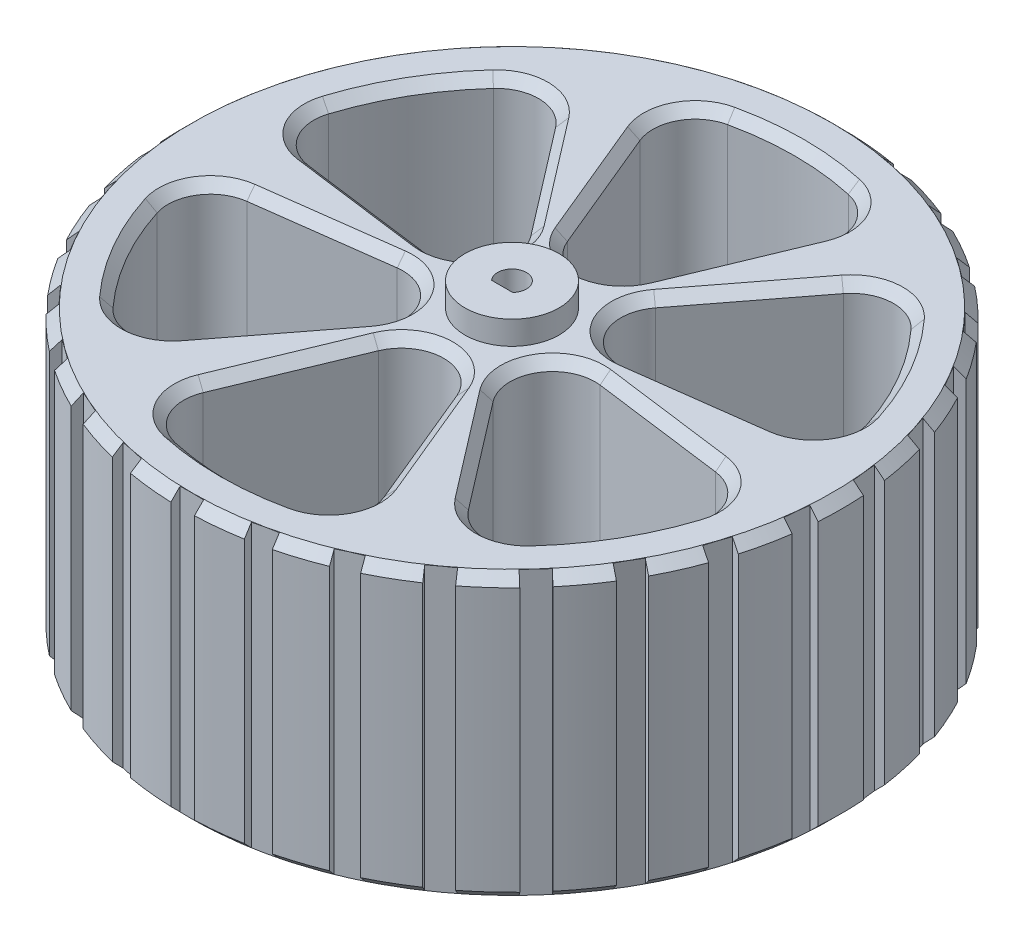
SolidWorks part; units mm, degrees
ref_plane "Front Plane" through (0, 0, 0) normal (0, 0, 1) x (1, 0, 0)
ref_plane "Top Plane" through (0, 0, 0) normal (0, 1, 0) x (1, 0, 0)
ref_plane "Right Plane" through (0, 0, 0) normal (1, 0, 0) x (0, 0, -1)
sketch "Sketch1" plane through (0, 0, 0) normal (0, 1, 0) x (1, 0, 0)
  line L0 (0, 0) -> (0, 30) construction
  line L1 (-4.1575, 10.037) -> (-9.6053, 23.1892)
  line L2 (4.1575, 10.037) -> (9.6053, 23.1892)
  line L3 (6.6136, 8.619) -> (15.2798, 19.913)
  line L4 (10.771, 1.418) -> (24.8851, 3.2762)
  line L5 (10.771, -1.418) -> (24.8851, -3.2762)
  line L6 (6.6136, -8.619) -> (15.2798, -19.913)
  line L7 (4.1575, -10.037) -> (9.6053, -23.1892)
  line L8 (-4.1575, -10.037) -> (-9.6053, -23.1892)
  line L9 (-6.6136, -8.619) -> (-15.2798, -19.913)
  line L10 (-10.771, -1.418) -> (-24.8851, -3.2762)
  line L11 (-10.771, 1.418) -> (-24.8851, 3.2762)
  line L12 (-6.6136, 8.619) -> (-15.2798, 19.913)
  arc A0 (6.4092, 29.3074) -> (-6.4092, 29.3074) centre (0, 0) ccw
  circle A1 centre (0, 0) radius 35
  arc A2 (-4.1575, 10.037) -> (4.1575, 10.037) centre (0, 11.7591) ccw
  arc A3 (9.6053, 23.1892) -> (6.4092, 29.3074) centre (5.4478, 24.9113) ccw
  arc A4 (-9.6053, 23.1892) -> (-6.4092, 29.3074) centre (-5.4478, 24.9113) cw
  arc A5 (28.5855, 9.1032) -> (22.1763, 20.2042) centre (0, 0) ccw
  arc A6 (15.2798, 19.913) -> (22.1763, 20.2042) centre (18.8499, 17.1736) cw
  arc A7 (24.8851, 3.2762) -> (28.5855, 9.1032) centre (24.2977, 7.7377) ccw
  arc A8 (6.6136, 8.619) -> (10.771, 1.418) centre (10.1837, 5.8795) ccw
  arc A9 (22.1763, -20.2042) -> (28.5855, -9.1032) centre (0, 0) ccw
  arc A10 (24.8851, -3.2762) -> (28.5855, -9.1032) centre (24.2977, -7.7377) cw
  arc A11 (15.2798, -19.913) -> (22.1763, -20.2042) centre (18.8499, -17.1736) ccw
  arc A12 (10.771, -1.418) -> (6.6136, -8.619) centre (10.1837, -5.8795) ccw
  arc A13 (-6.4092, -29.3074) -> (6.4092, -29.3074) centre (0, 0) ccw
  arc A14 (9.6053, -23.1892) -> (6.4092, -29.3074) centre (5.4478, -24.9113) cw
  arc A15 (-9.6053, -23.1892) -> (-6.4092, -29.3074) centre (-5.4478, -24.9113) ccw
  arc A16 (4.1575, -10.037) -> (-4.1575, -10.037) centre (0, -11.7591) ccw
  arc A17 (-28.5855, -9.1032) -> (-22.1763, -20.2042) centre (0, 0) ccw
  arc A18 (-15.2798, -19.913) -> (-22.1763, -20.2042) centre (-18.8499, -17.1736) cw
  arc A19 (-24.8851, -3.2762) -> (-28.5855, -9.1032) centre (-24.2977, -7.7377) ccw
  arc A20 (-6.6136, -8.619) -> (-10.771, -1.418) centre (-10.1837, -5.8795) ccw
  arc A21 (-22.1763, 20.2042) -> (-28.5855, 9.1032) centre (0, 0) ccw
  arc A22 (-24.8851, 3.2762) -> (-28.5855, 9.1032) centre (-24.2977, 7.7377) cw
  arc A23 (-15.2798, 19.913) -> (-22.1763, 20.2042) centre (-18.8499, 17.1736) ccw
  arc A24 (-10.771, 1.418) -> (-6.6136, 8.619) centre (-10.1837, 5.8795) ccw
  point P60 (0, 0)
  dimension "D1" = 60
  dimension "D4" = 70
  dimension "D5" = 4.5
  dimension "D2" = 22.5
  dimension "D3" = 22.5
  dimension "D6" = 6
extrude "Boss-Extrude1" add sketch "Sketch1" along normal blind 30
sketch "Sketch2" plane through (0, 0, 0) normal (0, -1, 0) x (1, 0, 0)
  line L0 (0, 0) -> (0, 35) construction
  line L1 (8.7075, 34.9534) -> (8.2917, 32.9971)
  line L2 (-1.25, 36) -> (1.25, 36)
  line L3 (-1.25, 36) -> (-1.25, 34)
  line L4 (-1.25, 34) -> (1.25, 34)
  line L5 (1.25, 36) -> (1.25, 34)
  line L6 (-1.25, 36) -> (1.25, 34) construction
  line L7 (-1.25, 34) -> (1.25, 36) construction
  line L8 (6.2621, 35.4732) -> (8.7075, 34.9534)
  line L9 (6.2621, 35.4732) -> (5.8463, 33.5169)
  line L10 (5.8463, 33.5169) -> (8.2917, 32.9971)
  line L11 (15.7845, 32.3792) -> (14.971, 30.5521)
  line L12 (13.5006, 33.3961) -> (15.7845, 32.3792)
  line L13 (13.5006, 33.3961) -> (12.6871, 31.569)
  line L14 (12.6871, 31.569) -> (14.971, 30.5521)
  line L15 (22.1715, 28.3899) -> (20.996, 26.7718)
  line L16 (20.149, 29.8593) -> (22.1715, 28.3899)
  line L17 (20.149, 29.8593) -> (18.9734, 28.2413)
  line L18 (18.9734, 28.2413) -> (20.996, 26.7718)
  line L19 (27.5896, 23.1598) -> (26.1033, 21.8215)
  line L20 (25.9168, 25.0176) -> (27.5896, 23.1598)
  line L21 (25.9168, 25.0176) -> (24.4305, 23.6794)
  line L22 (24.4305, 23.6794) -> (26.1033, 21.8215)
  line L23 (31.8019, 16.9175) -> (30.0699, 15.9175)
  line L24 (30.5519, 19.0825) -> (31.8019, 16.9175)
  line L25 (30.5519, 19.0825) -> (28.8199, 18.0825)
  line L26 (28.8199, 18.0825) -> (30.0699, 15.9175)
  line L27 (34.6243, 9.9358) -> (32.7222, 9.3178)
  line L28 (33.8518, 12.3134) -> (34.6243, 9.9358)
  line L29 (33.8518, 12.3134) -> (31.9497, 11.6954)
  line L30 (31.9497, 11.6954) -> (32.7222, 9.3178)
  line L31 (35.9334, 2.5199) -> (33.9444, 2.3108)
  line L32 (35.6721, 5.0062) -> (35.9334, 2.5199)
  line L33 (35.6721, 5.0062) -> (33.6831, 4.7971)
  line L34 (33.6831, 4.7971) -> (33.9444, 2.3108)
  line L35 (35.6721, -5.0062) -> (33.6831, -4.7971)
  line L36 (35.9334, -2.5199) -> (35.6721, -5.0062)
  line L37 (35.9334, -2.5199) -> (33.9444, -2.3108)
  line L38 (33.9444, -2.3108) -> (33.6831, -4.7971)
  line L39 (33.8518, -12.3134) -> (31.9497, -11.6954)
  line L40 (34.6243, -9.9358) -> (33.8518, -12.3134)
  line L41 (34.6243, -9.9358) -> (32.7222, -9.3178)
  line L42 (32.7222, -9.3178) -> (31.9497, -11.6954)
  line L43 (30.5519, -19.0825) -> (28.8199, -18.0825)
  line L44 (31.8019, -16.9175) -> (30.5519, -19.0825)
  line L45 (31.8019, -16.9175) -> (30.0699, -15.9175)
  line L46 (30.0699, -15.9175) -> (28.8199, -18.0825)
  line L47 (25.9168, -25.0176) -> (24.4305, -23.6794)
  line L48 (27.5896, -23.1598) -> (25.9168, -25.0176)
  line L49 (27.5896, -23.1598) -> (26.1033, -21.8215)
  line L50 (26.1033, -21.8215) -> (24.4305, -23.6794)
  line L51 (20.149, -29.8593) -> (18.9734, -28.2413)
  line L52 (22.1715, -28.3899) -> (20.149, -29.8593)
  line L53 (22.1715, -28.3899) -> (20.996, -26.7718)
  line L54 (20.996, -26.7718) -> (18.9734, -28.2413)
  line L55 (13.5006, -33.3961) -> (12.6871, -31.569)
  line L56 (15.7845, -32.3792) -> (13.5006, -33.3961)
  line L57 (15.7845, -32.3792) -> (14.971, -30.5521)
  line L58 (14.971, -30.5521) -> (12.6871, -31.569)
  line L59 (6.2621, -35.4732) -> (5.8463, -33.5169)
  line L60 (8.7075, -34.9534) -> (6.2621, -35.4732)
  line L61 (8.7075, -34.9534) -> (8.2917, -32.9971)
  line L62 (8.2917, -32.9971) -> (5.8463, -33.5169)
  line L63 (-1.25, -36) -> (-1.25, -34)
  line L64 (1.25, -36) -> (-1.25, -36)
  line L65 (1.25, -36) -> (1.25, -34)
  line L66 (1.25, -34) -> (-1.25, -34)
  line L67 (-8.7075, -34.9534) -> (-8.2917, -32.9971)
  line L68 (-6.2621, -35.4732) -> (-8.7075, -34.9534)
  line L69 (-6.2621, -35.4732) -> (-5.8463, -33.5169)
  line L70 (-5.8463, -33.5169) -> (-8.2917, -32.9971)
  line L71 (-15.7845, -32.3792) -> (-14.971, -30.5521)
  line L72 (-13.5006, -33.3961) -> (-15.7845, -32.3792)
  line L73 (-13.5006, -33.3961) -> (-12.6871, -31.569)
  line L74 (-12.6871, -31.569) -> (-14.971, -30.5521)
  line L75 (-22.1715, -28.3899) -> (-20.996, -26.7718)
  line L76 (-20.149, -29.8593) -> (-22.1715, -28.3899)
  line L77 (-20.149, -29.8593) -> (-18.9734, -28.2413)
  line L78 (-18.9734, -28.2413) -> (-20.996, -26.7718)
  line L79 (-27.5896, -23.1598) -> (-26.1033, -21.8215)
  line L80 (-25.9168, -25.0176) -> (-27.5896, -23.1598)
  line L81 (-25.9168, -25.0176) -> (-24.4305, -23.6794)
  line L82 (-24.4305, -23.6794) -> (-26.1033, -21.8215)
  line L83 (-31.8019, -16.9175) -> (-30.0699, -15.9175)
  line L84 (-30.5519, -19.0825) -> (-31.8019, -16.9175)
  line L85 (-30.5519, -19.0825) -> (-28.8199, -18.0825)
  line L86 (-28.8199, -18.0825) -> (-30.0699, -15.9175)
  line L87 (-34.6243, -9.9358) -> (-32.7222, -9.3178)
  line L88 (-33.8518, -12.3134) -> (-34.6243, -9.9358)
  line L89 (-33.8518, -12.3134) -> (-31.9497, -11.6954)
  line L90 (-31.9497, -11.6954) -> (-32.7222, -9.3178)
  line L91 (-35.9334, -2.5199) -> (-33.9444, -2.3108)
  line L92 (-35.6721, -5.0062) -> (-35.9334, -2.5199)
  line L93 (-35.6721, -5.0062) -> (-33.6831, -4.7971)
  line L94 (-33.6831, -4.7971) -> (-33.9444, -2.3108)
  line L95 (-35.6721, 5.0062) -> (-33.6831, 4.7971)
  line L96 (-35.9334, 2.5199) -> (-35.6721, 5.0062)
  line L97 (-35.9334, 2.5199) -> (-33.9444, 2.3108)
  line L98 (-33.9444, 2.3108) -> (-33.6831, 4.7971)
  line L99 (-33.8518, 12.3134) -> (-31.9497, 11.6954)
  line L100 (-34.6243, 9.9358) -> (-33.8518, 12.3134)
  line L101 (-34.6243, 9.9358) -> (-32.7222, 9.3178)
  line L102 (-32.7222, 9.3178) -> (-31.9497, 11.6954)
  line L103 (-30.5519, 19.0825) -> (-28.8199, 18.0825)
  line L104 (-31.8019, 16.9175) -> (-30.5519, 19.0825)
  line L105 (-31.8019, 16.9175) -> (-30.0699, 15.9175)
  line L106 (-30.0699, 15.9175) -> (-28.8199, 18.0825)
  line L107 (-25.9168, 25.0176) -> (-24.4305, 23.6794)
  line L108 (-27.5896, 23.1598) -> (-25.9168, 25.0176)
  line L109 (-27.5896, 23.1598) -> (-26.1033, 21.8215)
  line L110 (-26.1033, 21.8215) -> (-24.4305, 23.6794)
  line L111 (-20.149, 29.8593) -> (-18.9734, 28.2413)
  line L112 (-22.1715, 28.3899) -> (-20.149, 29.8593)
  line L113 (-22.1715, 28.3899) -> (-20.996, 26.7718)
  line L114 (-20.996, 26.7718) -> (-18.9734, 28.2413)
  line L115 (-13.5006, 33.3961) -> (-12.6871, 31.569)
  line L116 (-15.7845, 32.3792) -> (-13.5006, 33.3961)
  line L117 (-15.7845, 32.3792) -> (-14.971, 30.5521)
  line L118 (-14.971, 30.5521) -> (-12.6871, 31.569)
  line L119 (-6.2621, 35.4732) -> (-5.8463, 33.5169)
  line L120 (-8.7075, 34.9534) -> (-6.2621, 35.4732)
  line L121 (-8.7075, 34.9534) -> (-8.2917, 32.9971)
  line L122 (-8.2917, 32.9971) -> (-5.8463, 33.5169)
  circle A1 centre (0, 0) radius 35 construction
  point P130 (0, 0)
  dimension "D2" = 2
  dimension "D3" = 2.5
  dimension "D4" = 30
extrude "Cut-Extrude2" cut sketch "Sketch2" against normal blind 30
sketch "Sketch3" plane through (0, 0, 0) normal (0, -1, 0) x (1, 0, 0)
  circle A0 centre (0, 0) radius 5
  dimension "D1" = 10
extrude "Boss-Extrude2" add sketch "Sketch3" along normal blind 10 and the other way blind 32.5
sketch "Sketch4" plane through (0, -10, 0) normal (0, -1, 0) x (1, 0, 0)
  line L0 (-1.12, 1.042) -> (1.12, 1.042)
  arc A0 (-1.12, 1.042) -> (1.12, 1.042) centre (0, 0) ccw
  dimension "'" = 3.0596
  dimension "'Motor Hole Flat Face Length'" = 2.24
extrude "Cut-Extrude3" cut sketch "Sketch4" against normal through all both and the other way through all
sketch "Sketch5" plane through (0, 0, 1.042) normal (0, 0, -1) x (-1, 0, 0)
  line L0 (0, 0) -> (0, -10) construction
  line L1 (-5, -10) -> (5, -10) construction
  circle A0 centre (0, -5) radius 2.4914
  dimension "D1" = 4.9829
extrude "Cut-Extrude4" cut sketch "Sketch5" against normal blind 6 and the other way up to vertex (2.5718 mm away)
chamfer "Chamfer2" distance 1 angle 45 132 edges at (-6.2865, 0, -3.6295) (-10.9467, 0, -14.266) (-18.66, 0, -21.6696) (-25.9808, 0, -15) (-28.0964, 0, -5.3253) (-17.828, 0, -2.3471) (-6.2865, 30, -3.6295) (-10.9467, 30, -14.266) (-18.66, 30, -21.6696) (-25.9808, 30, -15) (-28.0964, 30, -5.3253) (-17.828, 30, -2.3471) (-6.2865, 0, 3.6295) (-17.828, 0, 2.3471) (-28.0964, 0, 5.3253) (-25.9808, 0, 15) (-18.66, 0, 21.6696) (-10.9467, 0, 14.266) (-6.2865, 30, 3.6295) (-17.828, 30, 2.3471) (-28.0964, 30, 5.3253) (-25.9808, 30, 15) (-18.66, 30, 21.6696) (-10.9467, 30, 14.266) (0, 0, 7.2591) (-6.8814, 0, 16.6131) (-9.4364, 0, 26.9949) (0, 0, 30) (9.4364, 0, 26.9949) (6.8814, 0, 16.6131) (0, 30, 7.2591) (-6.8814, 30, 16.6131) (-9.4364, 30, 26.9949) (0, 30, 30) (9.4364, 30, 26.9949) (6.8814, 30, 16.6131) (6.2865, 0, 3.6295) (10.9467, 0, 14.266) (18.66, 0, 21.6696) (25.9808, 0, 15) (28.0964, 0, 5.3253) (17.828, 0, 2.3471) (6.2865, 30, 3.6295) (10.9467, 30, 14.266) (18.66, 30, 21.6696) (25.9808, 30, 15) (28.0964, 30, 5.3253) (17.828, 30, 2.3471) (6.2865, 0, -3.6295) (17.828, 0, -2.3471) (28.0964, 0, -5.3253) (25.9808, 0, -15) (18.66, 0, -21.6696) (10.9467, 0, -14.266) (6.2865, 30, -3.6295) (17.828, 30, -2.3471) (28.0964, 30, -5.3253) (25.9808, 30, -15) (18.66, 30, -21.6696) (10.9467, 30, -14.266) (0, 0, -7.2591) (6.8814, 0, -16.6131) (9.4364, 0, -26.9949) (0, 0, -30) (-9.4364, 0, -26.9949) (-6.8814, 0, -16.6131) (0, 30, -7.2591) (6.8814, 30, -16.6131) (9.4364, 30, -26.9949) (0, 30, -30) (-9.4364, 30, -26.9949) (-6.8814, 30, -16.6131) (-3.6585, 0, 34.8083) (-10.8156, 0, 33.287) (-17.5, 0, 30.3109) (-23.4196, 0, 26.0101) (-28.3156, 0, 20.5725) (-31.9741, 0, 14.2358) (-34.2352, 0, 7.2769) (-35, 0, 0) (-34.2352, 0, -7.2769) (-31.9741, 0, -14.2358) (-28.3156, 0, -20.5725) (-23.4196, 0, -26.0101) (-17.5, 0, -30.3109) (-10.8156, 0, -33.287) (-3.6585, 0, -34.8083) (3.6585, 0, -34.8083) (10.8156, 0, -33.287) (17.5, 0, -30.3109) (23.4196, 0, -26.0101) (28.3156, 0, -20.5725) (31.9741, 0, -14.2358) (34.2352, 0, -7.2769) (35, 0, 0) (34.2352, 0, 7.2769) (31.9741, 0, 14.2358) (28.3156, 0, 20.5725) (17.5, 0, 30.3109) (10.8156, 0, 33.287) (3.6585, 0, 34.8083) (-3.6585, 30, 34.8083) (-10.8156, 30, 33.287) (-17.5, 30, 30.3109) (-23.4196, 30, 26.0101) (-28.3156, 30, 20.5725) (-31.9741, 30, 14.2358) (-34.2352, 30, 7.2769) (-35, 30, 0) (-34.2352, 30, -7.2769) (-31.9741, 30, -14.2358) (-28.3156, 30, -20.5725) (-23.4196, 30, -26.0101) (-17.5, 30, -30.3109) (-10.8156, 30, -33.287) (-3.6585, 30, -34.8083) (3.6585, 30, -34.8083) (10.8156, 30, -33.287) (17.5, 30, -30.3109) (23.4196, 30, -26.0101) (28.3156, 30, -20.5725) (31.9741, 30, -14.2358) (34.2352, 30, -7.2769) (35, 30, 0) (34.2352, 30, 7.2769) (31.9741, 30, 14.2358) (28.3156, 30, 20.5725) (23.4196, 30, 26.0101) (17.5, 30, 30.3109) (10.8156, 30, 33.287) (3.6585, 30, 34.8083) (23.4196, 0, 26.0101)
equation "\"Motor Hole Diameter\"=3.05958"
equation "\"'@Sketch4\"=\"Motor Hole Diameter\""
equation "\"'Motor Hole Flat Face Length'\"=2.75"
equation "\"'Motor Hole Flat Face Length'@Sketch4\"=2.24"
equation "\"Screw Diameter\"=4.98287"
equation "\"D1@Sketch5\"=\"Screw Diameter\""
